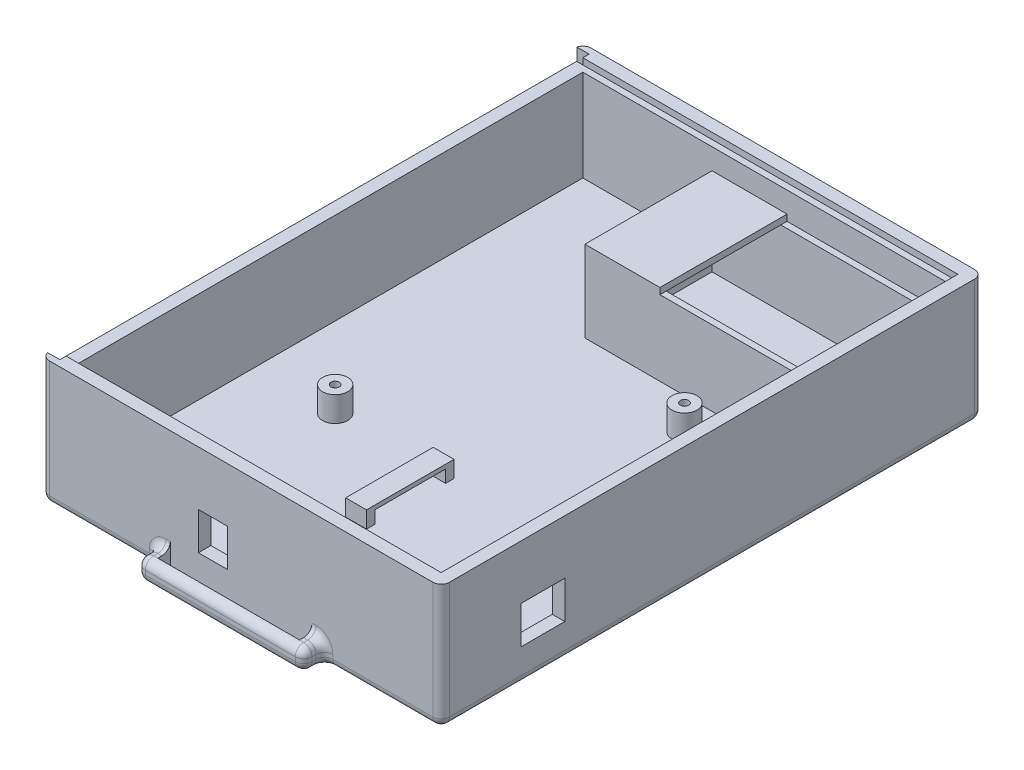
SolidWorks part; units mm, degrees
ref_plane "Piano frontale" through (0, 0, 0) normal (0, 0, 1) x (1, 0, 0)
ref_plane "Piano superiore" through (0, 0, 0) normal (0, 1, 0) x (1, 0, 0)
ref_plane "Piano destro" through (0, 0, 0) normal (1, 0, 0) x (0, 0, -1)
sketch "Schizzo1" plane through (0, 0, 0) normal (0, 1, 0) x (1, 0, 0)
  line L1 (0, 0) -> (96, 0)
  line L2 (0, 0) -> (0, 130)
  line L3 (0, 130) -> (96, 130)
  line L4 (96, 0) -> (96, 130)
  line L5 (0, 0) -> (96, 130) construction
  line L6 (0, 130) -> (96, 0) construction
  point P4 (48, 65)
  dimension "D1" = 96
  dimension "D2" = 130
sketch "Schizzo4" plane through (0, 0, 0) normal (0, 1, 0) x (1, 0, 0)
  line L0 (28, 130) -> (28, 135)
  line L1 (0, 130) -> (96, 130) construction
  line L2 (28, 135) -> (68, 135)
  line L3 (68, 135) -> (68, 130)
  line L4 (68, 130) -> (28, 130)
  line L5 (28, 0) -> (28, -5)
  line L6 (0, 0) -> (96, 0) construction
  line L7 (28, -5) -> (68, -5)
  line L8 (68, -5) -> (68, 0)
  line L9 (28, 0) -> (68, 0)
  point P5 (48, 135)
  dimension "D1" = 5
  dimension "D2" = 40
  dimension "D3" = 0
  dimension "D4" = 5
extrude "Esterno scatola" add sketch "Schizzo1" along normal blind 30
sketch "Schizzo5" plane through (0, 30, 0) normal (0, 1, 0) x (1, 0, 0)
  line L0 (0, 130) -> (0, 0) construction
  line L1 (3, 127) -> (93, 127)
  line L2 (3, 127) -> (3, 3)
  line L3 (3, 3) -> (93, 3)
  line L4 (93, 127) -> (93, 3)
  line L5 (3, 127) -> (93, 3) construction
  line L6 (3, 3) -> (93, 127) construction
  line L7 (96, 130) -> (0, 130) construction
  line L8 (96, 0) -> (96, 130) construction
  line L9 (0, 0) -> (96, 0) construction
  point P4 (48, 65)
  dimension "D1" = 3
  dimension "D2" = 3
  dimension "D3" = 3
  dimension "D4" = 3
extrude "Interno scatola" cut sketch "Schizzo5" against normal blind 25
extrude "Supporto lacci - esterno" add sketch "Schizzo4" along normal blind 5
sketch "Schizzo6" plane through (0, 5, 0) normal (0, 1, 0) x (1, 0, 0)
  line L0 (28, 130) -> (68, 130) construction
  line L1 (31, 130) -> (65, 130)
  line L2 (31, 130) -> (31, 133)
  line L3 (31, 133) -> (65, 133)
  line L4 (65, 130) -> (65, 133)
  line L5 (31, 130) -> (65, 133) construction
  line L6 (31, 133) -> (65, 130) construction
  line L7 (0, 0) -> (96, 0) construction
  line L8 (31, 0) -> (65, 0)
  line L9 (31, 0) -> (31, -3)
  line L10 (28, 135) -> (28, 130) construction
  line L11 (68, 130) -> (68, 135) construction
  line L12 (31, -3) -> (65, -3)
  line L13 (65, 0) -> (65, -3)
  line L14 (31, 0) -> (65, -3) construction
  line L15 (31, -3) -> (65, 0) construction
  line L16 (28, 0) -> (28, -5) construction
  line L17 (68, -5) -> (68, 0) construction
  point P4 (48, 131.5)
  point P15 (48, -1.5)
  point P20 (28, -2.5)
  dimension "D1" = 3
  dimension "D2" = 3
  dimension "D3" = 3
  dimension "D4" = 3
  dimension "D5" = 3
  dimension "D6" = 3
extrude "Supporto lacci - interno" cut sketch "Schizzo6" against normal through all
sketch "PCB" plane through (0, 5, 0) normal (0, 1, 0) x (1, 0, 0)
  line L0 (6, 6) -> (75, 6) construction
  line L1 (75, 6) -> (75, 91) construction
  line L2 (75, 91) -> (6, 91) construction
  line L3 (6, 91) -> (6, 6) construction
  line L5 (3, 127) -> (3, 3) construction
  line L6 (3, 3) -> (93, 3) construction
  dimension "D1" = 85
  dimension "D2" = 69
  dimension "D3" = 3
  dimension "D4" = 3
sketch "Schizzo8" plane through (0, 5, 0) normal (0, 1, 0) x (1, 0, 0)
  line L0 (75, 6) -> (75, 91) construction
  line L2 (6, 6) -> (75, 6) construction
  circle A0 centre (67.92, 86.47) radius 3
  circle A1 centre (67.92, 14.08) radius 3
  circle A2 centre (22.2, 48.37) radius 3
  dimension "D7" = 6
  dimension "D8" = 6
  dimension "D9" = 6
  dimension "D1" = 7.08
  dimension "D2" = 38.1
  dimension "D3" = 8.08
  dimension "D4" = 72.39
  dimension "D6" = 45.72
extrude "Viti" add sketch "Schizzo8" along normal blind 6
sketch "Schizzo9" plane through (0, 11, 0) normal (0, 1, 0) x (1, 0, 0)
  circle A0 centre (67.92, 86.47) radius 1
  circle A1 centre (67.92, 14.08) radius 1
  circle A2 centre (22.2, 48.37) radius 1
  dimension "D1" = 2
  dimension "D2" = 2
  dimension "D3" = 2
extrude "Vasatura viti" cut sketch "Schizzo9" against normal blind 5
sketch "Schizzo10" plane through (0, 5, 0) normal (0, 1, 0) x (1, 0, 0)
  line L0 (87, 123) -> (38, 123)
  line L19 (38, 123) -> (38, 95.5)
  line L20 (38, 95.5) -> (87, 95.5)
  line L21 (87, 95.5) -> (87, 94)
  line L22 (87, 94) -> (36.5, 94)
  line L23 (36.5, 94) -> (36.5, 124.5)
  line L24 (36.5, 124.5) -> (87, 124.5)
  line L25 (87, 124.5) -> (87, 123)
  line L30 (93, 3) -> (93, 127) construction
  line L31 (93, 127) -> (3, 127) construction
  dimension "D1" = 1.5
  dimension "D2" = 1.5
  dimension "D3" = 1.5
  dimension "D4" = 49
  dimension "D5" = 49
  dimension "D6" = 27.5
  dimension "D7" = 6
  dimension "D8" = 2.5
extrude "Vano batteria" add sketch "Schizzo10" along normal blind 18
sketch "Schizzo11" plane through (0, 23, 0) normal (0, 1, 0) x (1, 0, 0)
  line L0 (36.5, 94) -> (87, 94) construction
  line L1 (36.5, 124.5) -> (54.5, 124.5)
  line L2 (36.5, 124.5) -> (36.5, 94)
  line L3 (36.5, 94) -> (54.5, 94)
  line L4 (54.5, 124.5) -> (54.5, 94)
  line L5 (36.5, 124.5) -> (54.5, 94) construction
  line L6 (36.5, 94) -> (54.5, 124.5) construction
  point P4 (45.5, 109.25)
  dimension "D1" = 18
extrude "Blocco batteria" add sketch "Schizzo11" along normal blind 1.5
sketch "Schizzo12" plane through (0, 5, 0) normal (0, 1, 0) x (1, 0, 0)
  line L0 (93, 3) -> (93, 127) construction
  line L5 (45, 47.08) -> (50, 47.08)
  line L6 (45, 30.08) -> (50, 30.08)
  line L7 (45, 30.08) -> (45, 28.08)
  line L8 (45, 28.08) -> (50, 28.08)
  line L9 (50, 30.08) -> (50, 28.08)
  line L10 (45, 30.08) -> (50, 28.08) construction
  line L11 (45, 28.08) -> (50, 30.08) construction
  line L12 (45, 47.08) -> (45, 49.08)
  line L13 (45, 49.08) -> (50, 49.08)
  line L14 (50, 47.08) -> (50, 49.08)
  line L15 (45, 47.08) -> (50, 49.08) construction
  line L16 (45, 49.08) -> (50, 47.08) construction
  point P10 (47.5, 29.08)
  point P13 (47.5, 48.08)
  dimension "D5" = 17
  dimension "D1" = 5
  dimension "D2" = 43
  dimension "D4" = 2
  dimension "D6" = 2
  dimension "D8" = 5
extrude "Vano bluetooth" add sketch "Schizzo12" along normal blind 3
sketch "Schizzo13" plane through (0, 8, 0) normal (0, 1, 0) x (1, 0, 0)
  line L1 (45, 28.08) -> (50, 28.08)
  line L2 (45, 28.08) -> (45, 49.08)
  line L3 (45, 49.08) -> (50, 49.08)
  line L4 (50, 28.08) -> (50, 49.08)
  line L5 (45, 28.08) -> (50, 49.08) construction
  line L6 (45, 49.08) -> (50, 28.08) construction
  point P4 (47.5, 38.58)
extrude "Blocco bluetooth" add sketch "Schizzo13" along normal blind 1
sketch "Schizzo18" plane through (0, 0, 0) normal (-1, 0, 0) x (0, 0, 1)
  line L0 (-130, 30) -> (-130, 0) construction
  line L1 (-128.5, 28.5) -> (-1.5, 28.5)
  line L2 (-128.5, 28.5) -> (-128.5, 27)
  line L3 (-128.5, 27) -> (-1.5, 27)
  line L4 (-1.5, 28.5) -> (-1.5, 27)
  line L5 (-128.5, 28.5) -> (-1.5, 27) construction
  line L6 (-128.5, 27) -> (-1.5, 28.5) construction
  line L7 (0, 30) -> (0, 0) construction
  line L8 (-130, 30) -> (0, 30) construction
  point P4 (-65, 27.75)
  dimension "D1" = 1.5
  dimension "D2" = 1.5
  dimension "D3" = 1.5
  dimension "D4" = 1.5
extrude "Incastro coperchio" cut sketch "Schizzo18" against normal blind 94.5
sketch "Schizzo19" plane through (0, 0, 0) normal (-1, 0, 0) x (0, 0, 1)
  line L0 (-130, 30) -> (0, 30) construction
  line L1 (-128.5, 30) -> (-1.5, 30)
  line L2 (-128.5, 30) -> (-128.5, 28.5)
  line L3 (-128.5, 28.5) -> (-1.5, 28.5)
  line L4 (-1.5, 30) -> (-1.5, 28.5)
  line L5 (-128.5, 30) -> (-1.5, 28.5) construction
  line L6 (-128.5, 28.5) -> (-1.5, 30) construction
  point P4 (-65, 29.25)
extrude "Bordo rimosso per incastro coperchio" cut sketch "Schizzo19" against normal up to vertex (3 mm away) up to point (3, 5, -127)
sketch "Schizzo20" plane through (96, 0, 0) normal (1, 0, 0) x (0, 0, -1)
  line L0 (0, 0) -> (130, 0) construction
  line L1 (19.16, 17) -> (29.66, 17)
  line L2 (19.16, 17) -> (19.16, 8)
  line L3 (19.16, 8) -> (29.66, 8)
  line L4 (29.66, 17) -> (29.66, 8)
  line L5 (19.16, 17) -> (29.66, 8) construction
  line L6 (19.16, 8) -> (29.66, 17) construction
  line L7 (0, 30) -> (0, 0) construction
  point P4 (24.41, 12.5)
  dimension "D1" = 10.5
  dimension "D2" = 9
  dimension "D3" = 8
  dimension "D4" = 19.16
extrude "Vista LED laterale" cut sketch "Schizzo20" along direction (1, 0, 0) on the side against the normal up to next (3 mm away)
sketch "Schizzo21" plane through (0, 0, 0) normal (0, 0, 1) x (1, 0, 0)
  line L0 (28, 0) -> (68, 0) construction
  line L1 (37.75, 8) -> (44.75, 8)
  line L2 (37.75, 8) -> (37.75, 17)
  line L3 (37.75, 17) -> (44.75, 17)
  line L4 (44.75, 8) -> (44.75, 17)
  line L5 (37.75, 8) -> (44.75, 17) construction
  line L6 (37.75, 17) -> (44.75, 8) construction
  line L7 (0, 30) -> (0, 0) construction
  point P4 (41.25, 12.5)
  dimension "D1" = 7
  dimension "D2" = 9
  dimension "D3" = 8
  dimension "D4" = 41.25
extrude "Vista LED spessore" cut sketch "Schizzo21" along direction (0, 0, 1) on the side against the normal up to next (3 mm away)
fillet "Raccordo1" radius 2 42 edges at (66.5, 5, 0) (29.5, 5, 0) (66.5, 5, -130) (29.5, 5, -130) (68, 5, 2.5) (68, 2.5, 0) (48, 5, 5) (68, 2.5, 5) (28, 2.5, 0) (28, 5, 2.5) (28, 2.5, 5) (68, 2.5, -130) (68, 5, -132.5) (68, 2.5, -135) (48, 5, -135) (28, 2.5, -135) (28, 5, -132.5) (28, 2.5, -130) (14, 0, 0) (28, 0, 2.5) (48, 0, 5) (68, 0, 2.5) (82, 0, 0) (96, 0, -65) (82, 0, -130) (68, 0, -132.5) (48, 0, -135) (28, 0, -132.5) (14, 0, -130) (0, 0, -65) (48, 0, 0) (65, 0, 1.5) (48, 0, 3) (31, 0, 1.5) (48, 0, -133) (65, 0, -131.5) (48, 0, -130) (31, 0, -131.5) (0, 15, -130) (0, 15, 0) (96, 15, -130) (96, 15, 0)
